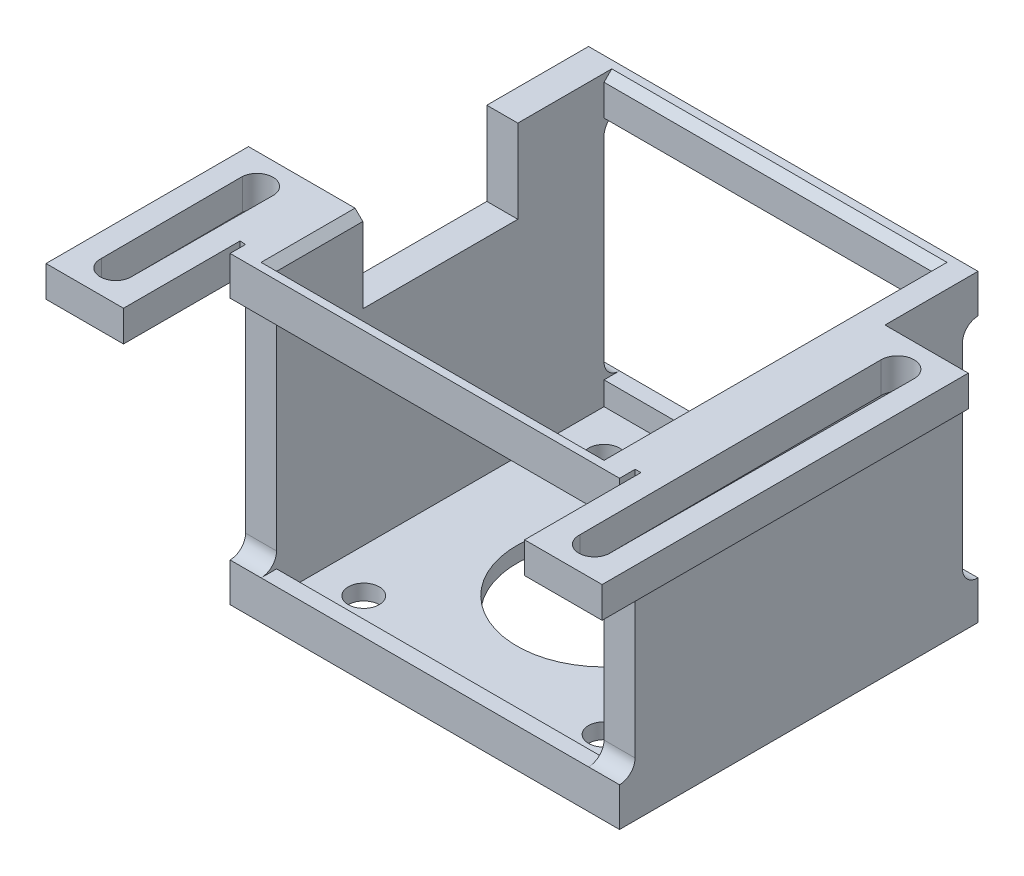
SolidWorks part; units mm, degrees
ref_plane "Front Plane" through (0, 0, 0) normal (0, 0, 1) x (1, 0, 0)
ref_plane "Top Plane" through (0, 0, 0) normal (0, 1, 0) x (1, 0, 0)
ref_plane "Right Plane" through (0, 0, 0) normal (1, 0, 0) x (0, 0, -1)
sketch "Sketch1" plane through (0, 0, 0) normal (0, 1, 0) x (1, 0, 0)
  line L1 (-21.125, -21.125) -> (21.125, -21.125)
  line L2 (-21.125, -21.125) -> (-21.125, 21.125)
  line L3 (-21.125, 21.125) -> (21.125, 21.125)
  line L4 (21.125, -21.125) -> (21.125, 21.125)
  line L5 (-21.125, -21.125) -> (21.125, 21.125) construction
  line L6 (-21.125, 21.125) -> (21.125, -21.125) construction
  point P0 (0, 0)
  dimension "D1" = 42.25
extrude "Boss-Extrude1" add sketch "Sketch1" along normal blind 2
sketch "Sketch7" plane through (0, 0, 0) normal (0, -1, 0) x (1, 0, 0)
  circle A0 centre (0, 0) radius 11.25
  dimension "D1" = 22.5
extrude "Cut-Extrude1" cut sketch "Sketch7" against normal up to next
sketch "Sketch9" plane through (0, 2, 0) normal (0, 1, 0) x (1, 0, 0)
  line L1 (-21.125, -21.125) -> (-25.125, -21.125)
  line L2 (-21.125, -21.125) -> (-21.125, 21.125)
  line L3 (-21.125, 21.125) -> (-25.125, 21.125)
  line L4 (-25.125, -21.125) -> (-25.125, 21.125)
  line L5 (0, 0) -> (-21.125, 0) construction
  line L8 (0, 0) -> (0, -33.6819) construction
  line L9 (21.125, 21.125) -> (25.125, 21.125)
  line L10 (25.125, -21.125) -> (25.125, 21.125)
  line L11 (21.125, -21.125) -> (25.125, -21.125)
  line L12 (21.125, -21.125) -> (21.125, 21.125)
  line L13 (-21.125, -21.125) -> (21.125, -21.125) construction
  line L14 (21.125, 21.125) -> (-21.125, 21.125) construction
  line L15 (-21.125, 21.125) -> (-21.125, -21.125) construction
  dimension "D3" = 4
extrude "Boss-Extrude6" add sketch "Sketch9" along normal blind 37.25 and the other way up to surface (2 mm away) other way up to face at (0, 0, -11.25)
sketch "Sketch8" plane through (0, 39.25, 0) normal (0, 1, 0) x (1, 0, 0)
  line L0 (30.875, -32.125) -> (30.875, 11.125) construction
  line L5 (0, 0) -> (0, -5.824) construction
  line L7 (-25.125, 21.125) -> (-25.125, -21.125) construction
  line L15 (-25.125, -21.125) -> (-25.125, 11.125)
  line L20 (-35.875, -36.125) -> (-35.875, 11.125)
  line L21 (-30.875, -32.125) -> (-30.875, 11.125) construction
  line L22 (-32.868, -31.9574) -> (-33, 7)
  line L23 (-28.8785, -32.0076) -> (-28.75, 7)
  line L32 (-35.875, -36.125) -> (-25.875, -36.125)
  line L33 (-21.125, -21.125) -> (21.125, -21.125) construction
  line L34 (-35.875, 11.125) -> (-25.125, 11.125)
  line L36 (-21.125, 21.125) -> (-25.125, 21.125) construction
  line L39 (-25.875, -36.125) -> (-25.875, -21.0855)
  line L40 (-25.875, -21.0855) -> (-25.125, -21.125)
  line L41 (25.875, -21.0855) -> (25.125, -21.125)
  line L42 (25.875, -36.125) -> (25.875, -21.0855)
  line L43 (35.875, 11.125) -> (25.125, 11.125)
  line L44 (35.875, -36.125) -> (25.875, -36.125)
  line L45 (28.8785, -32.0076) -> (28.75, 7)
  line L46 (32.868, -31.9574) -> (33, 7)
  line L47 (35.875, -36.125) -> (35.875, 11.125)
  line L48 (25.125, -21.125) -> (25.125, 11.125)
  arc A4 (-32.868, -31.9574) -> (-28.8785, -32.0076) centre (-30.875, -32.125) ccw
  arc A7 (-33, 7) -> (-28.75, 7) centre (-30.875, 7) cw
  arc A10 (33, 7) -> (28.75, 7) centre (30.875, 7) ccw
  arc A11 (32.868, -31.9574) -> (28.8785, -32.0076) centre (30.875, -32.125) cw
  point P9 (-30.875, -36.125)
  point P10 (-31, -7.5)
  point P14 (-31, 0.3126)
  point P21 (31, -7.5)
  point P26 (31, 0.3126)
  point P31 (31, 16)
  dimension "D2" = 2
  dimension "D4" = 2
  dimension "D1" = 15
  dimension "D3" = 10
  dimension "D5" = 2
  dimension "D6" = 0.75
  dimension "D7" = 10
extrude "Boss-Extrude7" add sketch "Sketch8" against normal blind 4
sketch "Sketch11" plane through (-25.125, 0, 0) normal (-1, 0, 0) x (0, -1, 0)
  line L0 (-35.5, -8) -> (-30.5, -8) construction
  line L1 (-35.5, 8) -> (-30.5, 8) construction
  line L2 (-35.5, -8) -> (-30.5, -8) construction
  line L3 (-35.5, 8) -> (-30.5, 8) construction
  line L4 (-39.25, -11.125) -> (-39.25, 36.125) construction
  line L5 (-28.5, 10) -> (-39.25, 10)
  line L6 (-28.5, 10) -> (-28.5, -10)
  line L7 (-28.5, -10) -> (-39.25, -10)
  line L8 (-39.25, 10) -> (-39.25, -10)
  dimension "D1" = 2
  dimension "D3" = 2
  dimension "D4" = 2
extrude "Cut-Extrude2" cut sketch "Sketch11" against normal up to next and the other way through all
sketch "Sketch12" plane through (0, 0, 21.125) normal (0, 0, 1) x (1, 0, 0)
  line L18 (-25.125, 39.25) -> (-21.125, 39.25) construction
  line L19 (-25.125, 39.25) -> (25.125, 39.25)
  line L20 (-25.125, 39.25) -> (-25.125, 34.25)
  line L21 (-25.125, 34.25) -> (25.125, 34.25)
  line L22 (25.125, 39.25) -> (25.125, 34.25)
  line L23 (25.125, 0) -> (25.125, 35.25) construction
  line L24 (-25.125, 0) -> (-25.125, 35.25) construction
  line L26 (-25.125, 0) -> (25.125, 0)
  line L27 (-25.125, 0) -> (-25.125, 5)
  line L28 (-25.125, 5) -> (25.125, 5)
  line L29 (25.125, 0) -> (25.125, 5)
  dimension "D1" = 5
extrude "Boss-Extrude8" add sketch "Sketch12" along normal blind 2
mirror "Mirror1" about plane through (0, 0, 0) normal (0, 0, 1) of "Boss-Extrude8"
fillet "Fillet2" radius 2 8 edges at (-23.125, 5, -21.125) (23.125, 5, -21.125) (23.125, 34.25, -21.125) (-23.125, 34.25, -21.125) (23.125, 34.25, 21.125) (23.125, 5, 21.125) (-23.125, 5, 21.125) (-23.125, 34.25, 21.125)
sketch "Sketch13" plane through (0, 2, 0) normal (0, -1, 0) x (1, 0, 0)
  circle A1 centre (15.5, 15.5) radius 1.5 construction
  circle A2 centre (15.5, -15.5) radius 1.5 construction
  circle A3 centre (-15.5, -15.5) radius 1.5 construction
  circle A4 centre (15.5, 15.5) radius 1.5 construction
  circle A5 centre (15.5, -15.5) radius 1.5 construction
  circle A6 centre (-15.5, -15.5) radius 1.5 construction
  circle A7 centre (-15.5, 15.5) radius 1.5 construction
  circle A8 centre (-15.5, 15.5) radius 1.5 construction
  circle A9 centre (-15.5, 15.5) radius 2
  circle A10 centre (15.5, 15.5) radius 2
  circle A11 centre (15.5, -15.5) radius 2
  circle A12 centre (-15.5, -15.5) radius 2
  dimension "D1" = 0.5
extrude "Cut-Extrude4" cut sketch "Sketch13" against normal through all both and the other way through all
chamfer "Chamfer1" distance 1 angle 45 3 edges at (0, 39.25, 21.125) (0, 39.25, -21.125) (21.125, 39.25, 0)
sketch "Sketch14" plane through (0, 35.25, 0) normal (0, -1, 0) x (1, 0, 0)
  line L0 (-25.125, -23.125) -> (-25.125, 23.125) construction
  line L1 (-25.125, -14.4295) -> (-38.0137, -14.4295)
  line L2 (-25.125, -14.4295) -> (-25.125, -8.4613)
  line L3 (-25.125, -8.4613) -> (-38.0137, -8.4613)
  line L4 (-38.0137, -14.4295) -> (-38.0137, -8.4613)
extrude "Cut-Extrude5" cut sketch "Sketch14" against normal up to next and the other way through all
sketch "Sketch15" plane through (0, 35.25, 0) normal (0, -1, 0) x (1, 0, 0)
  line L0 (-35.875, 10) -> (-35.875, 36.125) construction
  line L1 (-25.125, 10) -> (-35.875, 10)
  line L2 (-25.125, 10) -> (-25.125, 14)
  line L3 (-25.125, 14) -> (-28.8182, 14)
  line L4 (-35.875, 10) -> (-35.875, 14)
  line L5 (-32.9338, 14) -> (-35.875, 14)
  arc A0 (-32.9338, 14) -> (-28.8182, 14) centre (-30.876, 13.8982) ccw
  arc A1 (-28.8785, 32.0076) -> (-32.868, 31.9574) centre (-30.875, 32.125) ccw construction
  arc A3 (-28.8785, 32.0076) -> (-32.868, 31.9574) centre (-30.875, 32.125) ccw construction
extrude "Boss-Extrude9" add sketch "Sketch15" against normal up to surface (4 mm away) up to face at (30.8808, 39.25, 12.4956)
